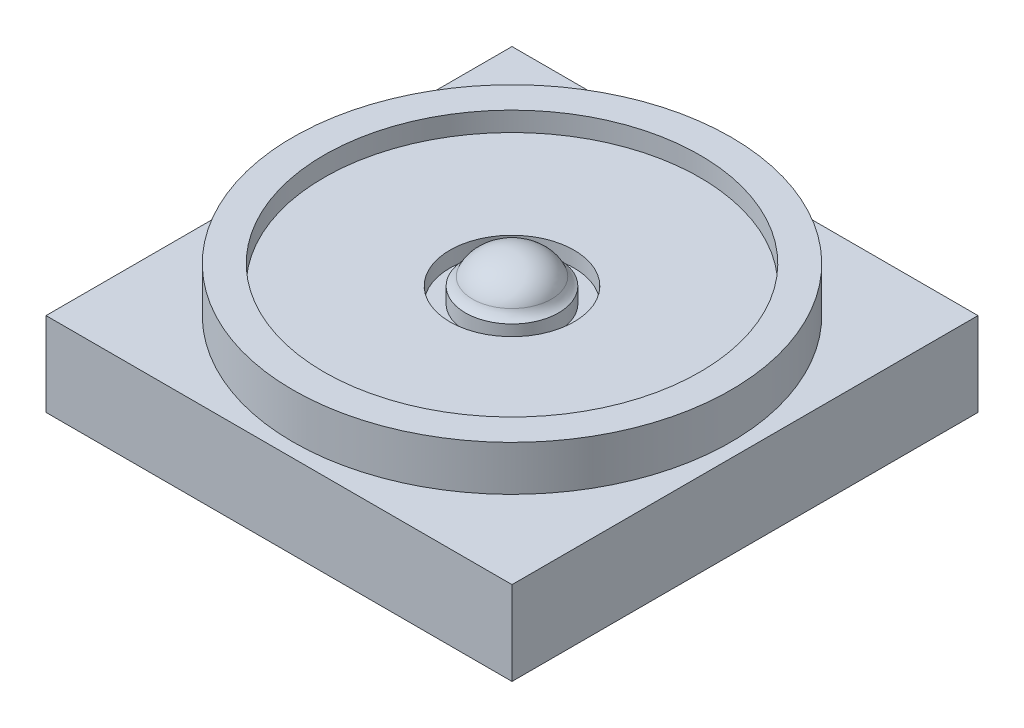
SolidWorks part; units mm, degrees
ref_plane "Front Plane" through (0, 0, 0) normal (0, 0, 1) x (1, 0, 0)
ref_plane "Top Plane" through (0, 0, 0) normal (0, 1, 0) x (1, 0, 0)
ref_plane "Right Plane" through (0, 0, 0) normal (1, 0, 0) x (0, 0, -1)
sketch "Sketch3" plane through (0, 0, 0) normal (0, 1, 0) x (1, 0, 0)
  line L1 (-15, -15) -> (15, -15)
  line L2 (-15, -15) -> (-15, 15)
  line L3 (-15, 15) -> (15, 15)
  line L4 (15, -15) -> (15, 15)
  line L5 (0, 15) -> (0, -15) construction
  line L6 (-15, 0) -> (15, 0) construction
  circle A0 centre (0, 0) radius 14.1
  circle A1 centre (0, 0) radius 12.1
  circle A2 centre (0, 0) radius 4
  circle A3 centre (0, 0) radius 3
  point P0 (0, 0)
  dimension "D3" = 28.2
  dimension "D4" = 24.2
  dimension "D5" = 8
  dimension "D6" = 6
  dimension "D2" = 30
extrude "Rectangle" add sketch "Sketch3" along normal blind 5.4 contours L1 L4 L3 L2 A0 region at (-14.5757, 0, 0)
extrude "Rim" add sketch "Sketch3<3>" along normal blind 8.3 contours A0 A1 region at (-13.7012, 0, 0)
sketch "Sketch3<3>" plane through (0, 0, 0) normal (0, 1, 0) x (1, 0, 0) same geometry as "Sketch3"
extrude "Flat_face" add sketch "Sketch3<5>" along normal blind 7.05 contours A1 A2 region at (-11.7578, 0, 0)
sketch "Sketch3<5>" plane through (0, 0, 0) normal (0, 1, 0) x (1, 0, 0) same geometry as "Sketch3"
extrude "Gap" add sketch "Sketch3<6>" along normal blind 6.05 contours A2 | A3
sketch "Sketch3<6>" plane through (0, 0, 0) normal (0, 1, 0) x (1, 0, 0) same geometry as "Sketch3"
extrude "Dome_face_outer" add sketch "Sketch3<7>" along normal blind 7.05 contours A3 region at (0, 0, 0)
sketch "Sketch3<7>" plane through (0, 0, 0) normal (0, 1, 0) x (1, 0, 0) same geometry as "Sketch3"
sketch "Sketch5" plane through (0, 7.05, 0) normal (0, 1, 0) x (1, 0, 0)
  circle A0 centre (0, 0) radius 2.64
  dimension "D1" = 5.28
extrude "Dome_face_inner" add sketch "Sketch5" along normal blind 0.001
dome "Dome" faces to dome 1 distance 1.95 reverse direction no elliptical dome yes face at (0, 7.051, 2.64) parameters "D1"=1.95
fillet "Dome_Fillet" radius 1.05 1 edges at (0, 7.05, 2.64)
sketch "Sketch6" plane through (0, 0, 0) normal (0, 1, 0) x (1, 0, 0)
  text T0 "ALL_OS_m"
extrude "Label" cut sketch "Sketch6" along normal blind 0.2
equation "\"Rectangle_Height\"= 5.4mm"
equation "\"Rectangle_Width\"= 30mm"
equation "\"Rim_OR\"= 14.1mm"
equation "\"Hole_OR\"= 4mm"
equation "\"Rim_Oh\"= 2.9mm'Outer height"
equation "\"Rim_Ih\"= 1.25mm"
equation "\"Hole_depth\"= 1mm"
equation "\"D2@Sketch3\"= \"Rectangle_Width\""
equation "\"D3@Sketch3\" = \"Rim_OR\" * 2"
equation "\"D5@Sketch3\"= \"Hole_OR\" * 2"
equation "\"D6@Sketch3\"= ( \"Hole_OR\" - 1 ) * 2"
equation "\"D4@Sketch3\" = ( \"Rim_OR\" - 2 ) * 2"
equation "\"D1@Rectangle\"= \"Rectangle_Height\""
equation "\"D1@Rim\"= \"Rectangle_Height\" + \"Rim_Oh\""
equation "\"D1@Flat_face\" = \"Rectangle_Height\" + \"Rim_Oh\" - \"Rim_Ih\""
equation "\"D1@Gap\" = \"Rectangle_Height\" + \"Rim_Oh\" - \"Rim_Ih\" - \"Hole_depth\""
equation "\"D1@Dome_face_outer\" = \"Rectangle_Height\" + \"Rim_Oh\" - \"Rim_Ih\""
equation "\"Dome_depth\" = 1.95mm'Param #2"
equation "\"D1@Sketch5\" = ( \"Hole_OR\" - 1 - \"Thicknss\" - \"min_width\" ) * 2"
equation "\"D1@Dome\" = \"Dome_depth\""
equation "\"D1@Dome_Fillet\"= ( \"Hole_OR\" - 1 ) - \"Dome_depth\""
equation "\"Thicknss\" = .31mm'Param #1"
equation "\"min_width\"= 0.05mm"
